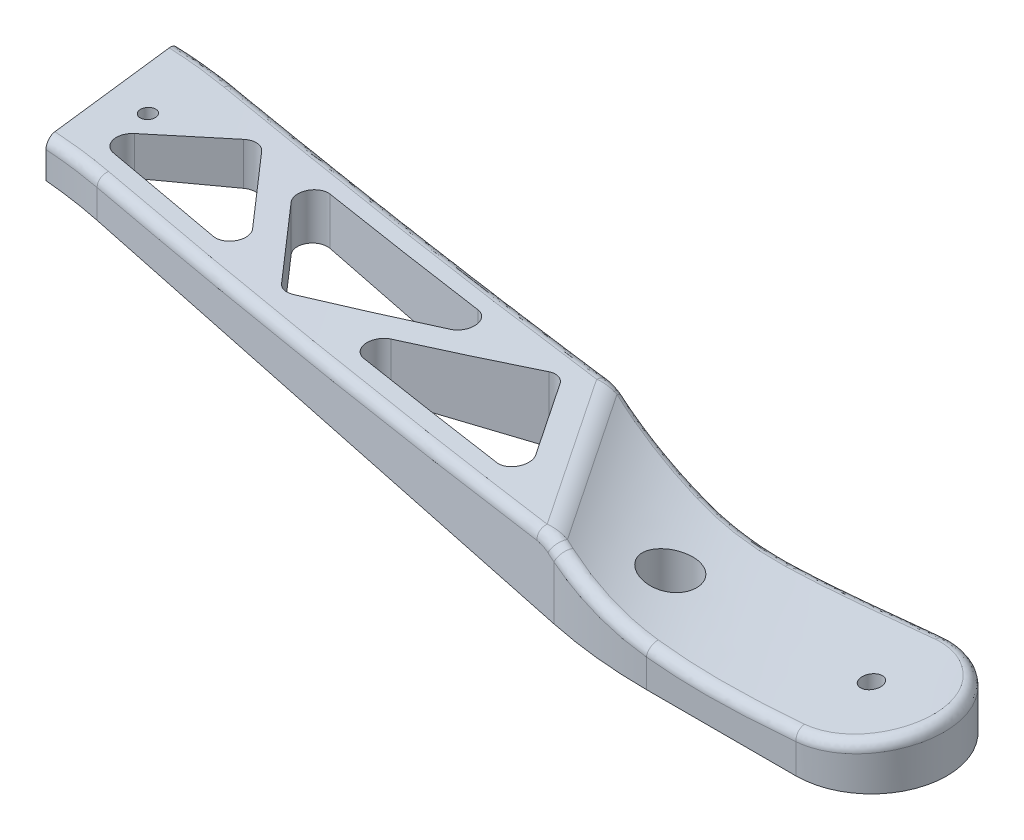
SolidWorks part; units mm, degrees
ref_plane "Front Plane" through (0, 0, 0) normal (0, 0, 1) x (1, 0, 0)
ref_plane "Top Plane" through (0, 0, 0) normal (0, 1, 0) x (1, 0, 0)
ref_plane "Right Plane" through (0, 0, 0) normal (1, 0, 0) x (0, 0, -1)
sketch "Sketch1" plane through (0, 0, 0) normal (0, 1, 0) x (1, 0, 0)
  line L0 (0, 0) -> (-350, 0) construction
  line L1 (0, 0) -> (40, 0) construction
  line L2 (0, 15) -> (40, 15)
  line L3 (0, -15) -> (40, -15)
  line L4 (-351.8754, 29.9413) -> (-333.2857, -24.9125) construction
  line L5 (-139.7849, 43.2259) -> (-4217.6379, -212.1962)
  line L6 (0, 15) -> (-4004.6012, 823.6244)
  line L7 (0, 15) -> (-5.9197, -13.7825) construction
  line L8 (-4217.6379, -212.1962) -> (-138.0533, 13.889)
  line L9 (-4004.6012, 823.6244) -> (-5.9197, -13.7825)
  line L10 (-333.2857, -24.9125) -> (-287.8235, 5.5889)
  line L11 (-5.9197, -13.7825) -> (0, -15)
  circle A0 centre (0, 0) radius 5
  circle A1 centre (-350, 0) radius 30
  circle A2 centre (40, 0) radius 2
  circle A3 centre (0, 0) radius 15
  circle A4 centre (40, 0) radius 15
  dimension "D1" = 10
  dimension "D4" = 4
  dimension "D5" = 60
  dimension "D6" = 30
  dimension "D7" = 165
  dimension "D2" = 350
  dimension "D3" = 40
  dimension "D8" = 165
  dimension "D9" = 135
  dimension "D10" = 150
extrude "Boss-Extrude1" add sketch "Sketch1" along normal blind 20 contours L8 A1 | A1 L8 | A1 L8 L9 L5 | A1 L10 L8 | A3 L6 L5 L9 | A3 A0 | A4 L2 A3 L3 | A4 A2 region at (-104.3815, 0, -20.1768) region at (20, 0, 0) region at (10.3066, 0, -10.3066) region at (50.3066, 0, -10.3066) region at (-256.3648, 0, -20.0554) region at (-350.7689, 0, -13.8751) region at (-310.7553, 0, 3.5404) region at (-349.359, 0, 11.5664)
fillet "Fillet1" radius 100 5 edges at (0, 10, -15) (-139.7849, 10, -43.2259) (-138.0533, 10, -13.889) (-287.8235, 10, -5.5889) (0, 10, 15)
ref_plane "Plane1" through (-86.3568, 0, -128.7144) normal (0.5571, 0, 0.8304) x (0.8304, 0, -0.5571)
sketch "Sketch3" plane through (-86.3568, 0, -128.7144) normal (0.5571, 0, 0.8304) x (0.8304, 0, -0.5571)
  line L0 (-290.646, 20) -> (-290.646, 0) construction
  line L1 (-290.646, 20) -> (-263.3377, 20) construction
  line L2 (-290.646, 20) -> (0.1568, 20)
  line L4 (48.2167, 0) -> (48.2167, 20) construction
  line L5 (0.1568, 20) -> (48.2167, 20)
  line L6 (48.2167, 20) -> (48.2167, 10)
  line L11 (0.1568, 20) -> (0.1568, 0) construction
  line L13 (48.2167, 0) -> (48.2167, 20) construction
  line L14 (48.2167, 7) -> (-242.9986, 7) construction
  line L15 (-15.6816, 0) -> (-15.6816, 20) construction
  spline S0 degree 2 poles (-290.646, 20) (-152.5347, -2.5394) (-15.6816, 14) knots 0 0 0 1 1 1
  spline S1 degree 3 poles (-15.6816, 14) (1.7787, 1.081) (32.0315, 10) (48.2167, 10) knots 0 0 0 0 1 1 1 1
  point P4 (48.2167, 7)
  dimension "D2" = 6
  dimension "D1" = 10
  dimension "D3" = 7
extrude "Cut-Extrude3" cut sketch "Sketch3" along normal blind 300 and the other way blind 131 contours L2 | L5 L6 region at (-173.4507, 14.5484, -70.2816)
fillet "Fillet3" radius 5 1 edges at (-21.8644, 14, -4.4422)
sketch "Sketch4" plane through (0, 0, 0) normal (0, 1, 0) x (1, 0, 0)
  line L0 (-23.8661, -4.9157) -> (-39.1031, 17.7949)
  line L1 (-39.1031, 17.7949) -> (-75.6397, 5.9268)
  line L2 (-75.6397, 5.9268) -> (-23.8661, -4.9157)
  line L3 (-125.1676, 11.1905) -> (-12.8731, -12.3263) construction
  line L4 (-12.8731, -12.3263) -> (-36.0971, 22.2889) construction
  line L5 (-49.0834, 19.8102) -> (-105.8384, 31.2704)
  line L6 (-105.8384, 31.2704) -> (-85.48, 7.9875)
  line L7 (-85.48, 7.9875) -> (-49.0834, 19.8102)
  line L8 (-36.0971, 22.2889) -> (-126.8801, 40.6201) construction
  line L9 (-113.9044, 32.8991) -> (-93.6107, 9.6903)
  line L10 (-93.6107, 9.6903) -> (-134.1835, 18.1871)
  line L11 (-134.1835, 18.1871) -> (-113.9044, 32.8991)
  line L12 (-127.4003, 35.6242) -> (-14.8981, 12.9074) construction
  line L13 (-134.1835, 18.1871) -> (-23.8661, -4.9157) construction
  line L14 (-150.6827, 37.5335) -> (-354.5716, 24.7626) construction
  line L15 (-143.9898, 18.5677) -> (-279.6875, 11.0475) construction
  line L16 (-260.4276, 7.1072) -> (-151.1984, 13.1605) construction
  line L17 (-152.9244, 42.4029) -> (-351.8754, 29.9413) construction
  line L18 (-143.9898, 18.5677) -> (-162.2437, 36.8094)
  line L19 (-162.2437, 36.8094) -> (-173.6392, 16.9246)
  line L20 (-173.6392, 16.9246) -> (-143.9898, 18.5677)
  line L21 (-168.2211, 36.435) -> (-179.5911, 16.5947)
  line L22 (-179.5911, 16.5947) -> (-198.1353, 34.5613)
  line L23 (-198.1353, 34.5613) -> (-168.2211, 36.435)
  line L24 (-186.3879, 16.218) -> (-204.8846, 34.1385)
  line L25 (-204.8846, 34.1385) -> (-219.6625, 14.374)
  line L26 (-219.6625, 14.374) -> (-186.3879, 16.218)
  line L27 (-211.4344, 33.7282) -> (-226.1755, 14.0131)
  line L28 (-226.1755, 14.0131) -> (-242.9353, 31.7551)
  line L29 (-242.9353, 31.7551) -> (-211.4344, 33.7282)
  line L30 (-232.7115, 13.6509) -> (-279.6875, 11.0475)
  line L31 (-279.6875, 11.0475) -> (-249.4292, 31.3484)
  line L32 (-249.4292, 31.3484) -> (-232.7115, 13.6509)
  line L33 (-150.6827, 37.5335) -> (-143.9898, 18.5677) construction
  line L34 (-143.9898, 18.5677) -> (-134.1835, 18.1871) construction
  line L35 (-127.4003, 35.6242) -> (-134.1835, 18.1871) construction
  line L37 (-259.3276, 30.7284) -> (-327.7673, -15.189)
  line L38 (-327.7673, -15.189) -> (-354.5716, 24.7626)
  line L39 (-366.7143, 24.9125) -> (-333.2857, -24.9125) construction
  line L40 (-333.2857, -24.9125) -> (-310.6084, -9.6979) construction
  line L41 (-354.5716, 24.7626) -> (-259.3276, 30.7284)
  line L42 (-364.7467, 9.4158) -> (-348.0325, -15.4967) construction
  circle A0 centre (-147.3362, 28.0506) radius 1.5
  circle A1 centre (-130.7919, 26.9057) radius 1.5
  circle A2 centre (-364.7467, 9.4158) radius 1.5
  circle A3 centre (-348.0325, -15.4967) radius 1.5
  dimension "D12" = 3
  dimension "D13" = 3
  dimension "D1" = 5
  dimension "D2" = 5
  dimension "D3" = 5
  dimension "D4" = 5
  dimension "D5" = 5
  dimension "D6" = 5
  dimension "D7" = 5
  dimension "D8" = 5
  dimension "D9" = 5
  dimension "D10" = 5
  dimension "D11" = 5
  dimension "D14" = 10
  dimension "D15" = 5
  dimension "D16" = 5
  dimension "D17" = 7
  dimension "D18" = 30
extrude "Cut-Extrude4" cut sketch "Sketch4" along normal blind 114 contours L41 L37 L38 | L32 L30 L31 | L29 L27 L28 | L26 L24 L25 | L23 L21 L22 | L20 L18 L19 | A1 | A0 | L11 L9 L10 | L7 L5 L6 | L2 L0 L1 | A3 | A2
fillet "Fillet4" radius 3 27 edges at (-23.8661, 6.5969, 4.9157) (-75.6397, 4.8538, -5.9268) (-39.1031, 6.5969, -17.7949) (-49.0834, 6.2031, -19.8102) (-85.48, 4.6031, -7.9875) (-105.8384, 4.4739, -31.2704) (-93.6107, 4.4153, -9.6903) (-134.1835, 3.7402, -18.1871) (-113.9044, 4.2984, -32.8991) (-143.9898, 3.6314, -18.5677) (-173.6392, 3.5024, -16.9246) (-162.2437, 3.5795, -36.8094) (-179.5911, 3.5172, -16.5947) (-198.1353, 3.5474, -34.5613) (-168.2211, 3.5395, -36.435) (-204.8846, 3.5971, -34.1385) (-186.3879, 3.5507, -16.218) (-219.6625, 3.9702, -14.374) (-242.9353, 4.2066, -31.7551) (-226.1755, 4.1019, -14.0131) (-211.4344, 3.6621, -33.7282) (-279.6875, 5.7968, -11.0475) (-232.7115, 4.2504, -13.6509) (-249.4292, 4.3664, -31.3484) (-259.3276, 4.6413, -30.7284) (-354.5716, 9.2095, -24.7626) (-327.7673, 9.2095, 15.189)
sketch "Sketch5" plane through (0, 0, 0) normal (0, 1, 0) x (1, 0, 0)
  line L0 (0, 131.8931) -> (0, -132.9054) construction
  line L1 (-149.5876, 131.7171) -> (-120.5615, -144.4481)
  line L2 (0, 0) -> (-8.1263, 77.3162) construction
  line L3 (-149.5876, 131.7171) -> (-434.6413, 42.4032)
  line L4 (-434.6413, 42.4032) -> (-303.3894, -167.7836)
  line L5 (-303.3894, -167.7836) -> (-120.5615, -144.4481)
  dimension "D1" = 6
  dimension "D2" = 135
extrude "Cut-Extrude5" cut sketch "Sketch5" along normal blind 133
fillet "Fillet5" radius 2 13 edges at (-11.5501, 13.7975, 12.6034) (54.9077, 9.8825, 1.6619) (-33.696, 13.6799, -21.804)
